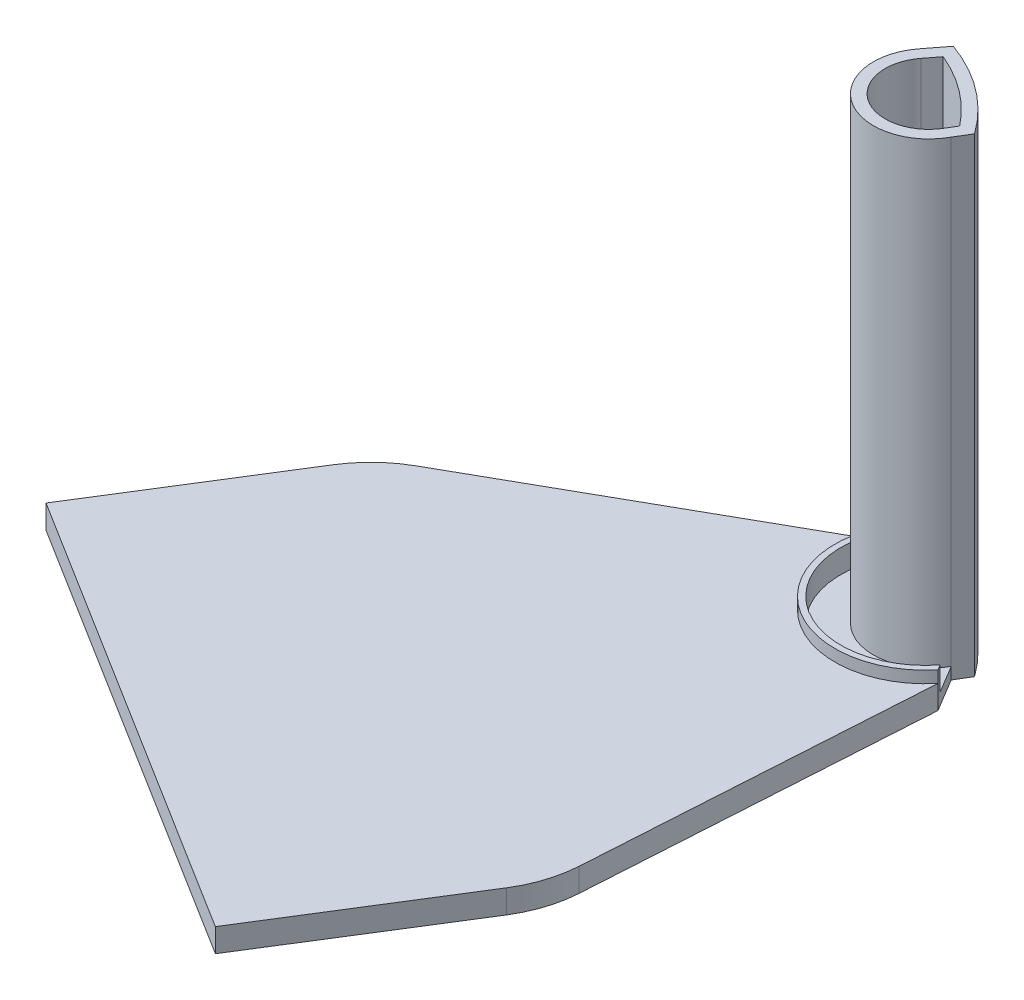
SolidWorks part; units mm, degrees
ref_plane "Alzado" through (0, 0, 0) normal (0, 0, 1) x (1, 0, 0)
ref_plane "Planta" through (0, 0, 0) normal (0, 1, 0) x (1, 0, 0)
ref_plane "Vista lateral" through (0, 0, 0) normal (1, 0, 0) x (0, 0, -1)
sketch "Croquis3" plane through (0, 0, 0) normal (0, 1, 0) x (1, 0, 0)
  line L0 (-8.0359, 0.8886) -> (-4.6602, 0.7384)
  line L1 (3.2253, -4.3817) -> (4.9174, -7.2023)
  arc A3 (-8.0359, 0.8886) -> (4.9174, -7.2023) centre (-1.0355, -2.3184) ccw
  arc A4 (-4.6602, 0.7384) -> (3.2253, -4.3817) centre (-0.9235, -2.1391) ccw
  point P3 (3.3037, -4.2303)
extrude "Saliente-Extruir3" add sketch "Croquis3" along normal blind 1
sketch "Croquis1" plane through (0, 0, 0) normal (0, 1, 0) x (1, 0, 0)
  line L2 (-4.6602, 0.7384) -> (-3.3811, 2.3993)
  line L3 (3.2253, -4.3817) -> (3.9762, -3.1511)
  line L5 (-3.8679, 0.1282) -> (-3.0435, 1.1987)
  line L6 (2.3572, -3.8845) -> (2.7699, -3.2081)
  arc A5 (-4.6602, 0.7384) -> (3.2253, -4.3817) centre (-0.9235, -2.1391) ccw construction
  arc A6 (-4.6602, 0.7384) -> (3.2253, -4.3817) centre (-0.9235, -2.1391) ccw
  arc A9 (2.7699, -3.2081) -> (-3.0435, 1.1987) centre (-8.5312, -12.0786) ccw
  arc A10 (-3.8679, 0.1282) -> (2.3572, -3.8845) centre (-0.9235, -2.1391) ccw
  arc A14 (3.9762, -3.1511) -> (-3.3811, 2.3993) centre (-8.5312, -12.0786) ccw
  point P0 (3.9762, -3.1511)
  point P6 (-3.2918, 2.7074)
  point P17 (4.2126, -2.4814)
  point P18 (0, 0)
  point P19 (0, 0)
  dimension "D1" = 1
sketch "Croquis4" plane through (0, 1, 0) normal (0, 1, 0) x (1, 0, 0)
  line L6 (-4.6602, 0.7384) -> (-8.0359, 0.8886) construction
  line L7 (4.9174, -7.2023) -> (3.2253, -4.3817) construction
  line L8 (4.9174, -7.2023) -> (4.643, -6.745)
  line L9 (-7.4938, 0.8645) -> (-8.0359, 0.8886)
  arc A1 (-8.0359, 0.8886) -> (4.9174, -7.2023) centre (-1.0355, -2.3184) ccw
  arc A3 (-8.0359, 0.8886) -> (4.9174, -7.2023) centre (-1.0355, -2.3184) ccw construction
  arc A4 (-7.4938, 0.8645) -> (4.643, -6.745) centre (-1.0355, -2.3184) ccw
  arc A5 (-7.5813, 0.6803) -> (4.643, -6.745) centre (-1.0355, -2.3184) ccw construction
  arc A6 (-8.0359, 0.8886) -> (5.0373, -7.0524) centre (-1.0355, -2.3184) ccw construction
  dimension "D1" = 0.5
extrude "Saliente-Extruir4" add sketch "Croquis4" along normal blind 2
extrude "Saliente-Extruir5" add sketch "Croquis1" along normal blind 40
sketch "Croquis8" plane through (0, 0, 0) normal (0, -1, 0) x (1, 0, 0)
  line L1 (1.6217, 40.6146) -> (-7.9036, 55.8584)
  line L2 (-7.9036, 55.8584) -> (-46.3202, 31.853)
  line L3 (-46.3202, 31.853) -> (-36.9131, 16.7986)
  line L4 (-33.3457, 13.3879) -> (-8.0359, -0.8886)
  line L5 (3.1218, 35.939) -> (4.9174, 7.2023)
  circle A0 centre (-10.4107, 42.2642) radius 7.65
  circle A1 centre (-33.0027, 28.1471) radius 7.65
  arc A2 (3.1218, 35.939) -> (1.6217, 40.6146) centre (-6.8587, 35.3154) ccw
  arc A3 (-33.3457, 13.3879) -> (-36.9131, 16.7986) centre (-28.4327, 22.0978) cw
  arc M11 (4.9174, 7.2023) -> (-8.0359, -0.8886) centre (-1.0355, 2.3184) ccw
  dimension "D1" = 15.3
  dimension "D2" = 15.3
  dimension "D4" = 10
  dimension "D3" = 26.64
  dimension "D5" = 45.3
  dimension "D6" = 9.33
extrude "Saliente-Extruir6" add sketch "Croquis8" against normal blind 2 contours A3 L4 L5 A2 L1 L2 L3 A1 A0 M11 | A0 | A1 region at (-15.4364, 0, 25.2515) region at (-10.4107, 0, 42.2642)
